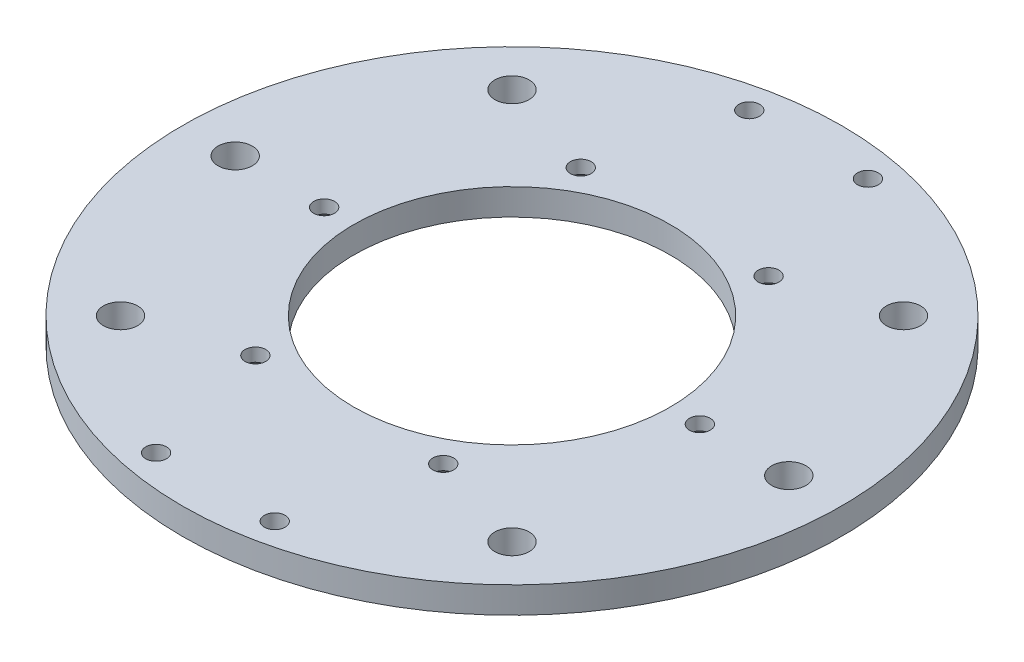
SolidWorks part; units mm, degrees
ref_plane "Спереди" through (0, 0, 0) normal (0, 0, 1) x (1, 0, 0)
ref_plane "Сверху" through (0, 0, 0) normal (0, 1, 0) x (1, 0, 0)
ref_plane "Справа" through (0, 0, 0) normal (1, 0, 0) x (0, 0, -1)
sketch "Эскиз1" plane through (0, 0, 0) normal (0, 1, 0) x (1, 0, 0)
  circle A0 centre (0, 0) radius 24
  circle A1 centre (0, 0) radius 50
  dimension "D1" = 48
  dimension "D2" = 100
extrude "Бобышка-Вытянуть1" add sketch "Эскиз1" along normal blind 4
hole_wizard "Сверло под метчик  спиральное M31" positions "Эскиз2" profile "Эскиз3" hole size "M3x0.5" standard "DIN"
sketch "Эскиз2" plane through (0, 4, 0) normal (0, 1, 0) x (1, 0, 0)
  point P0 (28.5, 0)
  dimension "D1" = 28.5
sketch "Эскиз3" plane through (28.5, 4, 0) normal (1, 0, 0) x (0, 0, 1)
  line L0 (0, 0) -> (0, 8.9464)
  line L1 (0, 8.9464) -> (1.575, 8)
  line L2 (1.575, 8) -> (1.575, 0)
  line L5 (1.575, 0) -> (0, 0)
  line L10 (0, 8.9464) -> (-1.575, 8) construction
  line L11 (0, -6.35) -> (0, 107.95) construction
  dimension "Диаметр отверстия" = 3.15
  dimension "Глубина отверстия" = 8
  dimension "Угол заточки сверла" = 118
pattern_circular "Круговой массив1" count 6 over 360 about axis through (0, 4, 0) along (0, 1, 0) of "Сверло под метчик  спиральное M31"
chamfer "Фаска1" distance 2 angle 45 6 edges at (-14.25, 0, 26.2567) (-28.5, 0, 1.575) (-14.25, 0, -23.1067) (14.25, 0, -23.1067) (28.5, 0, 1.575) (14.25, 0, 26.2567)
hole_wizard "Сверло под метчик  спиральное M32" positions "Эскиз4" profile "Эскиз5" hole size "M3x0.5" standard "DIN" end condition through all
sketch "Эскиз4" plane through (0, 0, 0) normal (0, -1, 0) x (-1, 0, 0)
  point P0 (-9, -45)
  dimension "D1" = 9
  dimension "D2" = 45
sketch "Эскиз5" plane through (9, 0, 45) normal (1, 0, 0) x (0, 0, -1)
  line L0 (0, 0) -> (0, 4)
  line L1 (0, 4) -> (1.575, 4)
  line L2 (1.575, 4) -> (1.575, 0)
  line L5 (1.575, 0) -> (0, 0)
  line L11 (0, -6.35) -> (0, 107.95) construction
  dimension "Диаметр сквозного отверстия" = 3.15
  dimension "Глубина сквозного отверстия" = 4
sketch "Эскиз6" plane through (0, 0, 0) normal (0, 1, 0) x (1, 0, 0)
  line L0 (0, 0) -> (0, 15.2777) construction
  line L1 (0, 0) -> (-12.2514, 0) construction
pattern_linear "Линейный массив1" count 2 spacing 18 along (-1, 0, 0) count 2 spacing 90 along (0, 0, -1) of "Сверло под метчик  спиральное M32"
hole_wizard "Сверло под метчик  спиральное M52" positions "Эскиз11" profile "Эскиз12" hole size "M5x0.8" standard "DIN" end condition through all
sketch "Эскиз11" plane through (0, 0, 0) normal (0, -1, 0) x (-1, 0, 0)
  point P0 (42, 0)
  point P2 (-42, 0)
  dimension "D1" = 42
  dimension "D2" = 42
sketch "Эскиз12" plane through (-42, 0, 0) normal (1, 0, 0) x (0, 0, -1)
  line L0 (0, 0) -> (0, 4)
  line L1 (0, 4) -> (2.6, 4)
  line L2 (2.6, 4) -> (2.6, 0)
  line L5 (2.6, 0) -> (0, 0)
  line L11 (0, -6.35) -> (0, 107.95) construction
  dimension "Диаметр сквозного отверстия" = 5.2
  dimension "Глубина сквозного отверстия" = 4
pattern_circular "Круговой массив3" count 2 every 45 about axis through (0, 0, 0) along (0, 1, 0) of "Сверло под метчик  спиральное M52" other way count 2
